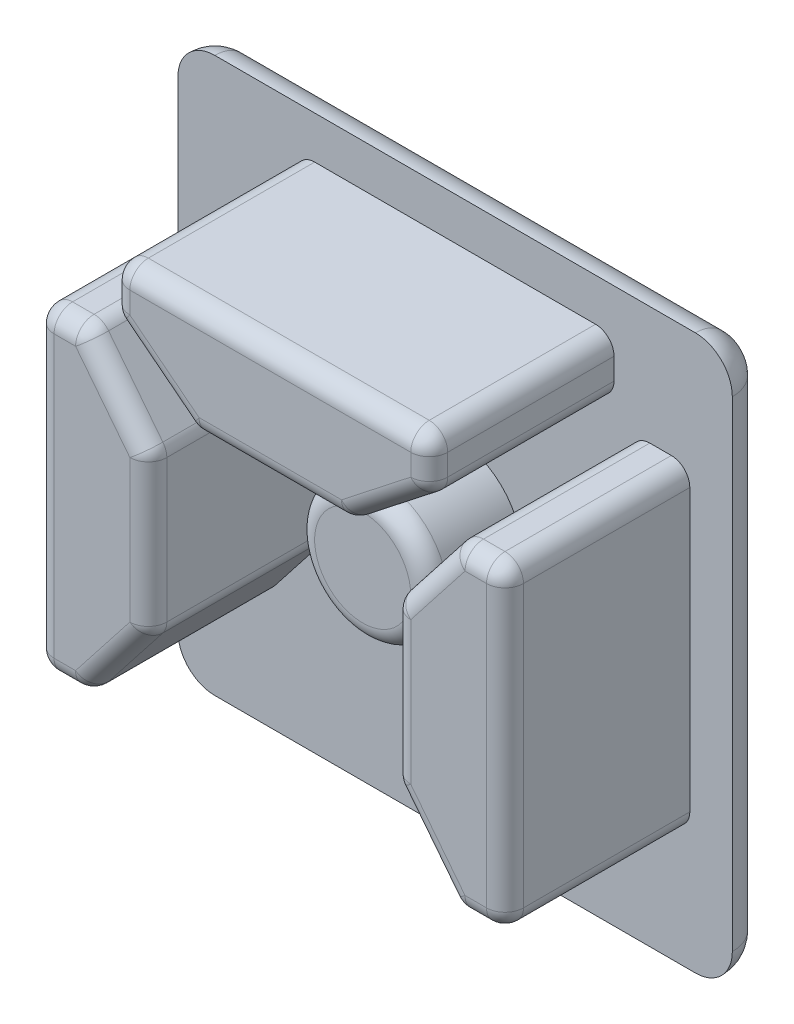
SolidWorks part; units mm, degrees
ref_plane "Plan de face" through (0, 0, 0) normal (0, 0, 1) x (1, 0, 0)
ref_plane "Plan de dessus" through (0, 0, 0) normal (0, 1, 0) x (1, 0, 0)
ref_plane "Plan de droite" through (0, 0, 0) normal (1, 0, 0) x (0, 0, -1)
sketch "Esquisse1" plane through (0, 0, 0) normal (0, 0, 1) x (1, 0, 0)
  line L1 (0, 0) -> (30, 0)
  line L2 (0, 0) -> (0, 30)
  line L3 (0, 30) -> (30, 30)
  line L4 (30, 0) -> (30, 30)
  dimension "D1" = 30
  dimension "D2" = 30
extrude "Boss.-Extru.1" add sketch "Esquisse1" along normal blind 2
sketch "Esquisse5" plane through (0, 0, 2) normal (0, 0, 1) x (1, 0, 0)
  line L0 (27.7, 6.4) -> (27.7, 23.6)
  line L1 (27.7, 23.6) -> (25.05, 23.6)
  line L2 (25.05, 23.6) -> (21.6, 19.2)
  line L3 (21.6, 19.2) -> (21.6, 10.8)
  line L4 (21.6, 10.8) -> (25.05, 6.4)
  line L5 (25.05, 6.4) -> (27.7, 6.4)
  line L6 (0, 0) -> (30, 0) construction
  line L8 (30, 0) -> (30, 30) construction
  dimension "D5" = 2.3
  dimension "D1" = 17.2
  dimension "D2" = 6.1
  dimension "D3" = 8.4
  dimension "D4" = 4.4
  dimension "D6" = 6.4
  dimension "D7" = 2.65
  dimension "D8" = 2.65
extrude "Boss.-Extru.5" add sketch "Esquisse5" along normal blind 10
fillet "Congé1" radius 1 6 edges at (27.7, 6.4, 7) (27.7, 23.6, 7) (25.05, 6.4, 7) (21.6, 10.8, 7) (21.6, 19.2, 7) (25.05, 23.6, 7)
sketch "Esquisse2" plane through (0, 0, 2) normal (0, 0, 1) x (1, 0, 0)
  line L0 (0, 0) -> (30, 0) construction
  line L1 (0, 30) -> (0, 0) construction
  circle A0 centre (15, 15) radius 3.6
  dimension "D1" = 15
  dimension "D2" = 15
extrude "Boss.-Extru.6" add sketch "Esquisse2" along normal blind 5
pattern_circular "Répétition circulaire1" count 3 every 90 about axis through (15, 15, 7) along (0, 0, 1) of "Congé1", "Boss.-Extru.5"
fillet "Congé2" radius 2 4 edges at (30, 0, 1) (0, 0, 1) (30, 30, 1) (0, 30, 1)
fillet "Congé3" radius 1 37 edges at (18.6, 15, 7) (25.0991, 6.5008, 12) (23.2814, 8.6556, 12) (21.6548, 10.8189, 12) (21.6, 15, 12) (21.6548, 19.1811, 12) (23.2814, 21.3444, 12) (25.0991, 23.4992, 12) (26.1183, 23.6, 12) (27.4071, 23.3071, 12) (27.7, 15, 12) (27.4071, 6.6929, 12) (26.1183, 6.4, 12) (23.4992, 25.0991, 12) (21.3444, 23.2814, 12) (19.1811, 21.6548, 12) (15, 21.6, 12) (10.8189, 21.6548, 12) (8.6556, 23.2814, 12) (6.5008, 25.0991, 12) (6.4, 26.1183, 12) (6.6929, 27.4071, 12) (15, 27.7, 12) (23.3071, 27.4071, 12) (23.6, 26.1183, 12) (4.9009, 23.4992, 12) (6.7186, 21.3444, 12) (8.3452, 19.1811, 12) (8.4, 15, 12) (8.3452, 10.8189, 12) (6.7186, 8.6556, 12) (4.9009, 6.5008, 12) (3.8817, 6.4, 12) (2.5929, 6.6929, 12) (2.3, 15, 12) (2.5929, 23.3071, 12) (3.8817, 23.6, 12)
fillet "Congé4" radius 2 8 edges at (29.4142, 29.4142, 0) (15, 30, 0) (0.5858, 29.4142, 0) (0, 15, 0) (0.5858, 0.5858, 0) (15, 0, 0) (29.4142, 0.5858, 0) (30, 15, 0)
